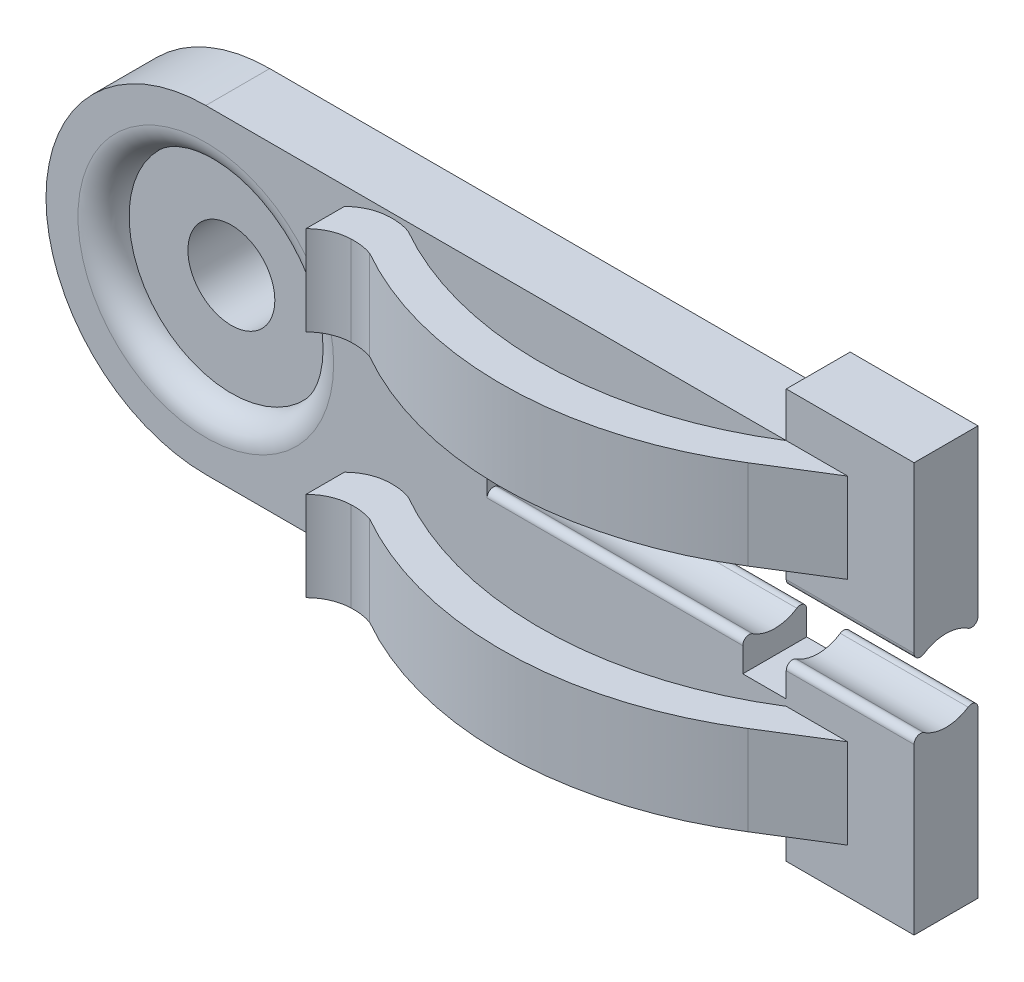
SolidWorks part; units mm, degrees
ref_plane "Front Plane" through (0, 0, 0) normal (0, 0, 1) x (1, 0, 0)
ref_plane "Top Plane" through (0, 0, 0) normal (0, 1, 0) x (1, 0, 0)
ref_plane "Right Plane" through (0, 0, 0) normal (1, 0, 0) x (0, 0, -1)
sketch "Sketch1" plane through (0, 0, 0) normal (0, 0, 1) x (1, 0, 0)
  line L0 (0, -6.25) -> (22.7, -6.25)
  line L1 (-12.7, 12.7) -> (12.7, 12.7)
  line L2 (-12.7, 12.7) -> (-12.7, -12.7)
  line L3 (-12.7, -12.7) -> (12.7, -12.7)
  line L4 (12.7, 12.7) -> (12.7, -12.7)
  line L5 (0, 6.25) -> (22.7, 6.25)
  line L6 (22.7, 6.25) -> (22.7, -6.25)
  circle A0 centre (0, 0) radius 1.7
  arc A1 (0, 6.25) -> (0, -6.25) centre (0, 0) ccw
  dimension "D1" = 3.4
  dimension "D3" = 25.4
  dimension "D4" = 25.4
  dimension "D5" = 12.7
  dimension "D6" = 12.7
  dimension "D7" = 10
extrude "Boss-Extrude1" add sketch "Sketch1" along normal blind 2.5 contours L5 A1 L0 L4 A0 | L6 L5 L4 L0 region at (4.0056, 0, 0) region at (17.7, 0, 0)
sketch "Sketch2" plane through (0, 0, 2.5) normal (0, 0, 1) x (1, 0, 0)
  line L1 (22.7, -8) -> (27.7, -8)
  line L2 (22.7, -8) -> (22.7, 8)
  line L3 (22.7, 8) -> (27.7, 8)
  line L4 (27.7, -8) -> (27.7, 8)
  circle A0 centre (0, 0) radius 1.7 construction
  dimension "D1" = 5
  dimension "D2" = 16
  dimension "D3" = 8
extrude "Boss-Extrude2" add sketch "Sketch2" against normal blind 2.5
sketch "Sketch3" plane through (0, 0, 2.5) normal (0, 0, 1) x (1, 0, 0)
  line L0 (22.7, 8) -> (22.7, 6.25) construction
  line L1 (22.7, 2.5) -> (21, 2.5)
  line L2 (22.7, 2.5) -> (22.7, -2.5)
  line L3 (22.7, -2.5) -> (21, -2.5)
  line L4 (21, 2.5) -> (21, -2.5)
  circle A0 centre (0, 0) radius 1.7 construction
  dimension "D1" = 1.7
  dimension "D2" = 0
  dimension "D3" = 5
  dimension "D4" = 2.5
extrude "Cut-Extrude1" cut sketch "Sketch3" against normal through all
sketch "Sketch6" plane through (27.7, 0, 0) normal (1, 0, 0) x (0, 0, -1)
  line L0 (-2.5, -8) -> (-2.5, 8) construction
  line L1 (0, -8) -> (-2.5, -8) construction
  line L2 (0, 8) -> (-2.5, 8) construction
  circle A0 centre (-1.25, 0) radius 1.59
  point P6 (-1.25, 8)
  dimension "D4" = 3.18
  dimension "D1" = 1.25
  dimension "D2" = 8
  dimension "D3" = 8
extrude "Cut-Extrude3" cut sketch "Sketch6" against normal blind 16.7
sketch "Sketch7" plane through (0, -6.25, 0) normal (0, -1, 0) x (1, 0, 0)
  line L1 (6.1299, 3.2107) -> (6.1299, 4.7107)
  line L3 (22.7, 4) -> (22.7, 2.5)
  arc A0 (22.7, 2.5) -> (8.2067, 2.7997) centre (15.2027, -9.4701) ccw
  arc A1 (7.3606, 2.6809) -> (6.1299, 3.2107) centre (7.409, 4.4878) cw
  arc A2 (7.3606, 2.6809) -> (8.2067, 2.7997) centre (7.4758, 4.9321) ccw
  arc A3 (7.3606, 4.1809) -> (6.1299, 4.7107) centre (7.409, 5.9878) cw
  arc A4 (22.7, 4) -> (8.2067, 4.2997) centre (15.2027, -7.9701) ccw
  arc A5 (7.3606, 4.1809) -> (8.2067, 4.2997) centre (7.4758, 6.4321) ccw
  dimension "D3" = 2
  dimension "D1" = 1.5
extrude "Boss-Extrude3" add sketch "Sketch7" against normal blind 3.5 separate body
sketch "Sketch9" plane through (0, -6.25, 0) normal (0, -1, 0) x (1, 0, 0)
  line L0 (22.7, 4) -> (25.1049, 2.5)
  line L1 (25.1049, 2.5) -> (22.7, 2.5)
  line L2 (22.7, 2.5) -> (22.7, 4)
extrude "Boss-Extrude5" add sketch "Sketch9" against normal blind 3.5 separate body
combine bodies "Combine1" operation type add bodies to combine 111 106
ref_plane "Plane1" through (0, 0, 0) normal (0, -1, 0) x (-1, 0, 0)
mirror "Mirror5" about plane through (0, 0, 0) normal (0, -1, 0) of bodies 112
combine bodies "Combine4" operation type add bodies to combine 105 112 116
sketch "Sketch10" plane through (0, 0, 0) normal (0, 0, -1) x (-1, 0, 0)
  circle A0 centre (0, 0) radius 4
  dimension "D1" = 8
extrude "Boss-Extrude6" add sketch "Sketch10" along normal blind 1.875
sketch "Sketch11" plane through (0, 0, 0) normal (0, 0, 1) x (1, 0, 0)
  circle A0 centre (0, 0) radius 1.7
extrude "Cut-Extrude4" cut sketch "Sketch11" against normal through all
sketch "Sketch12" plane through (0, 0, 2.5) normal (0, 0, 1) x (1, 0, 0)
  circle A0 centre (0, 0) radius 4
  dimension "D1" = 8
extrude "Cut-Extrude5" cut sketch "Sketch12" against normal blind 1
fillet "Fillet1" radius 1 1 edges at (4, 0, 2.5)
fillet "Fillet2" radius 1 1 edges at (-4, 0, -1.875)
fillet "Fillet3" radius 0.25 4 edges at (16, -0.9826, 0) (16, 0.9826, 0) (16, 0.9826, 2.5) (16, -0.9826, 2.5)
fillet "Fillet4" radius 0.25 4 edges at (25.2, 0.9826, 0) (25.2, 0.9826, 2.5) (25.2, -0.9826, 0) (25.2, -0.9826, 2.5)
